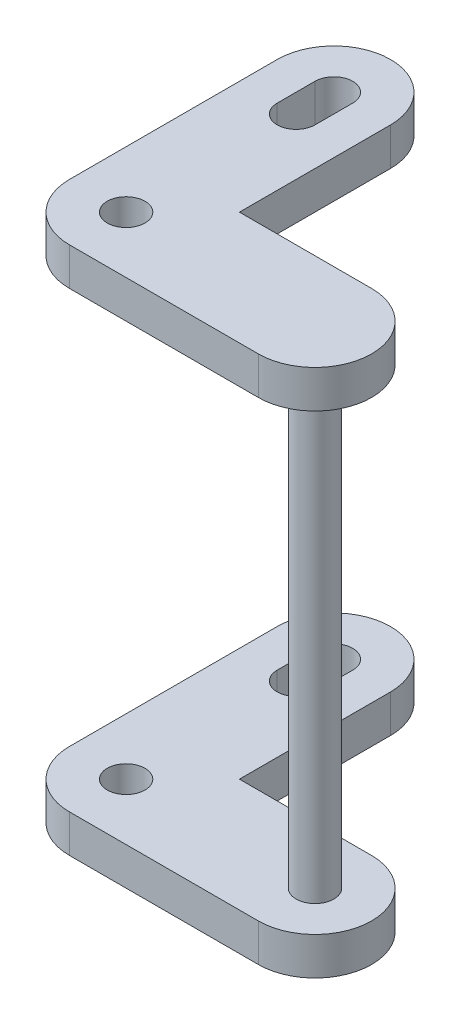
SolidWorks part; units mm, degrees
ref_plane "Front Plane" through (0, 0, 0) normal (0, 0, 1) x (1, 0, 0)
ref_plane "Top Plane" through (0, 0, 0) normal (0, 1, 0) x (1, 0, 0)
ref_plane "Right Plane" through (0, 0, 0) normal (1, 0, 0) x (0, 0, -1)
sketch "Sketch1" plane through (0, 0, 0) normal (0, 1, 0) x (1, 0, 0)
  line L0 (5, -1) -> (1.5, -1)
  line L2 (-1.5, 2.5) -> (-1.5, -2.5)
  line L4 (1.5, 2.5) -> (1.5, -1)
  line L5 (-1.5, 2.5) -> (1.5, -2.5) construction
  line L6 (-1.5, -2.5) -> (1.5, 2.5) construction
  line L7 (5, -4) -> (0, -4)
  line L8 (5, -1) -> (0, -4) construction
  line L9 (0, -1) -> (5, -4) construction
  line L10 (0, -2.5) -> (1.5, -2.5) construction
  line L11 (0, -2.5) -> (0, -4) construction
  line L12 (-0.5, 3) -> (-0.5, 2)
  line L13 (0.5, 3) -> (0.5, 2)
  line L14 (-1.5, 2.5) -> (-1.5, 3)
  line L15 (1.5, 3) -> (1.5, 2.5)
  arc A1 (-1.5, -2.5) -> (0, -4) centre (0, -2.5) ccw
  circle A2 centre (0, -2.5) radius 0.5
  arc A4 (5, -4) -> (5, -1) centre (5, -2.5) ccw
  arc A8 (0.5, 3) -> (-0.5, 3) centre (0, 3) ccw
  arc A9 (-0.5, 2) -> (0.5, 2) centre (0, 2) ccw
  arc A10 (1.5, 3) -> (-1.5, 3) centre (0, 3) ccw
  point P0 (0, 0)
  point P12 (2.5, -2.5)
  dimension "D3" = 1
  dimension "D1" = 3
  dimension "D2" = 5
  dimension "D6" = 90
  dimension "D5" = 2
extrude "Boss-Extrude1" add sketch "Sketch1" along normal blind 1
sketch "Sketch2" plane through (0, 1, 0) normal (0, 1, 0) x (1, 0, 0)
  circle A0 centre (5, -2.5) radius 0.5
extrude "Boss-Extrude2" add sketch "Sketch2" along normal blind 12
sketch "Sketch3" plane through (0, 13, 0) normal (0, 1, 0) x (1, 0, 0)
  line L0 (1.5, -1) -> (5, -1)
  line L1 (5, -4) -> (0, -4)
  line L2 (-1.5, -2.5) -> (-1.5, 2.5)
  line L3 (1.5, 2.5) -> (1.5, -1)
  line L4 (-0.5, 3) -> (-0.5, 2)
  line L5 (0.5, 3) -> (0.5, 2)
  line L6 (-1.5, 3) -> (-1.5, 2.5)
  line L7 (1.5, 3) -> (1.5, 2.5)
  arc A0 (5, -1) -> (5, -4) centre (5, -2.5) cw
  arc A1 (0, -4) -> (-1.5, -2.5) centre (0, -2.5) cw
  circle A4 centre (0, -2.5) radius 0.5
  arc A5 (0.5, 3) -> (-0.5, 3) centre (0, 3) ccw
  arc A6 (-0.5, 2) -> (0.5, 2) centre (0, 2) ccw
  arc A7 (1.5, 3) -> (-1.5, 3) centre (0, 3) ccw
  point P12 (0, 0)
  point P17 (0, 0)
  point P31 (0, 0)
  point P32 (0, 0)
extrude "Boss-Extrude3" add sketch "Sketch3" along normal blind 1
